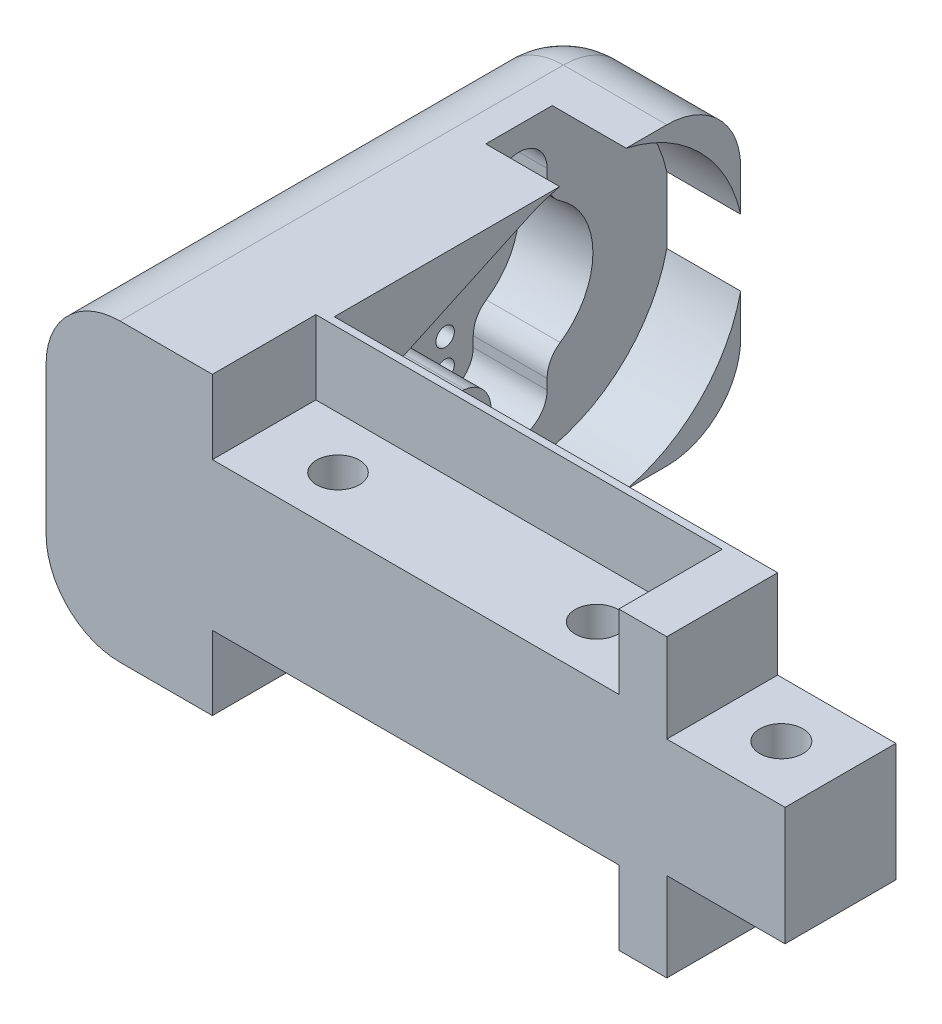
SolidWorks part; units mm, degrees
ref_plane "Спереди" through (0, 0, 0) normal (0, 0, 1) x (1, 0, 0)
ref_plane "Сверху" through (0, 0, 0) normal (0, 1, 0) x (1, 0, 0)
ref_plane "Справа" through (0, 0, 0) normal (1, 0, 0) x (0, 0, -1)
sketch "Эскиз1" plane through (0, 0, 0) normal (0, 1, 0) x (1, 0, 0)
  line L0 (-13, 27.5) -> (-13, 0)
  line L1 (-25, -7.5) -> (25, -7.5)
  line L2 (-25, -7.5) -> (-25, 27.5)
  line L3 (-25, 27.5) -> (-13, 27.5)
  line L4 (25, -7.5) -> (25, 27.5)
  line L5 (-25, -7.5) -> (25, 27.5) construction
  line L6 (-25, 27.5) -> (25, -7.5) construction
  line L7 (-13, 0) -> (13, 0)
  line L8 (13, 0) -> (13, 27.5)
  line L9 (13, 27.5) -> (25, 27.5)
  dimension "D1" = 27.5
  dimension "D2" = 50
  dimension "D3" = 26
  dimension "D4" = 35
extrude "Бобышка-Вытянуть1" add sketch "Эскиз1" along normal blind 20
fillet "Скругление1" radius 5 10 edges at (25, 0, -10) (25, 20, -10) (-25, 20, -10) (-25, 0, -10) (19, 20, -27.5) (25, 10, -27.5) (19, 0, -27.5) (-25, 10, -27.5) (-19, 20, -27.5) (-19, 0, -27.5)
sketch "Эскиз2" plane through (13, 0, 0) normal (-1, 0, 0) x (0, 0, 1)
  line L0 (-1030, 10) -> (48970, 10) construction
  line L1 (-27.5, 5) -> (-27.5, 15) construction
  circle A0 centre (-17.5, 10) radius 8
  point P5 (-27.5, 10)
  dimension "D1" = 16
  dimension "D2" = 10
extrude "Вырез-Вытянуть1" cut sketch "Эскиз2" against normal blind 5
sketch "Эскиз3" plane through (18, 0, 0) normal (-1, 0, 0) x (0, 0, 1)
  circle A0 centre (-17.5, 10) radius 6
  circle A1 centre (-17.5, 10) radius 8 construction
  dimension "D1" = 12
extrude "Вырез-Вытянуть2" cut sketch "Эскиз3" against normal blind 1
sketch "Эскиз4" plane through (-13, 0, 0) normal (1, 0, 0) x (0, 0, -1)
  line L0 (-1015, 10) -> (48985, 10) construction
  line L1 (-7.5, 15) -> (-7.5, 5) construction
  line L2 (13.195, 19.3021) -> (2.9, 14.5376)
  line L3 (2.9, 5.4624) -> (13.195, 0.6979)
  arc A0 (13.195, 0.6979) -> (13.195, 19.3021) centre (17.5, 10) ccw
  circle A1 centre (17.5, 10) radius 8 construction
  arc A2 (2.9, 14.5376) -> (2.9, 5.4624) centre (5, 10) ccw
  point P7 (-7.5, 10)
  dimension "D1" = 20.5
  dimension "D2" = 12.5
  dimension "D3" = 5
extrude "Вырез-Вытянуть3" cut sketch "Эскиз4" against normal blind 5
sketch "Эскиз5" plane through (-18, 0, 0) normal (1, 0, 0) x (0, 0, -1)
  line L0 (19.4, 15.8129) -> (19.4, 16.4984)
  line L1 (15.6, 16.4984) -> (15.6, 15.6654)
  line L2 (13.8328, 13.679) -> (1.9323, 12.2844)
  line L3 (1.9323, 7.7156) -> (13.8328, 6.321)
  line L4 (15.6, 4.3346) -> (15.6, 3.5016)
  line L5 (19.4, 3.5016) -> (19.4, 4.1871)
  arc A0 (19.4, 16.4984) -> (15.6, 16.4984) centre (17.5, 16.4984) ccw
  arc A1 (1.9323, 12.2844) -> (1.9323, 7.7156) centre (2.2, 10) ccw
  arc A2 (15.6, 3.5016) -> (19.4, 3.5016) centre (17.5, 3.5016) ccw
  arc A4 (20.2857, 14.1521) -> (20.2857, 5.8479) centre (17.5, 10) cw
  arc A5 (15.6, 4.3346) -> (13.8328, 6.321) centre (13.6, 4.3346) ccw
  arc A6 (15.6, 15.6654) -> (13.8328, 13.679) centre (13.6, 15.6654) cw
  arc A7 (20.2857, 5.8479) -> (19.4, 4.1871) centre (21.4, 4.1871) ccw
  arc A8 (20.2857, 14.1521) -> (19.4, 15.8129) centre (21.4, 15.8129) cw
  arc A9 (15.25, 20) -> (13.195, 19.3021) centre (17.5, 10) ccw construction
  arc A10 (15.25, 20) -> (13.195, 19.3021) centre (17.5, 10) ccw construction
  dimension "D3" = 2.3
  dimension "D4" = 1.9
  dimension "D5" = 5
  dimension "D8" = 2
  dimension "D9" = 2
  dimension "D1" = 3.8
  dimension "D2" = 15.3
  dimension "D6" = 12.9968
  dimension "D7" = 0.833
extrude "Вырез-Вытянуть4" cut sketch "Эскиз5" against normal blind 5
sketch "Эскиз6" plane through (-23, 0, 0) normal (1, 0, 0) x (0, 0, -1)
  line L0 (-990.222, 10) -> (49009.778, 10) construction
  line L1 (22.5, 5) -> (22.5, 15) construction
  line L2 (17.5, -985.0921) -> (17.5, 49014.9079) construction
  circle A0 centre (2.278, 10) radius 0.625
  circle A1 centre (6.3111, 10) radius 0.625
  circle A2 centre (10.4282, 10) radius 0.625
  circle A3 centre (17.5, 14.9079) radius 0.625
  circle A4 centre (17.5, 16.8489) radius 0.625
  circle A5 centre (17.5, 5.0821) radius 0.625
  circle A6 centre (17.5, 3.1411) radius 0.625
  point P11 (24009.778, 10)
  point P14 (22.5, 10)
  dimension "D1" = 1.25
  dimension "D2" = 4.0331
  dimension "D3" = 4.1171
  dimension "D4" = 12.0718
  dimension "D5" = 4.9079
  dimension "D6" = 1.9409
  dimension "D7" = 4.9179
  dimension "D8" = 1.9409
  dimension "D9" = 5
extrude "Вырез-Вытянуть5" cut sketch "Эскиз6" against normal blind 4
sketch "Эскиз7" plane through (0, 0, 7.5) normal (0, 0, 1) x (1, 0, 0)
  line L0 (-20, 20) -> (20, 20) construction
  line L1 (-13.75, 20) -> (13.75, 20)
  line L2 (-13.75, 20) -> (-13.75, 15)
  line L3 (-13.75, 15) -> (13.75, 15)
  line L4 (13.75, 20) -> (13.75, 15)
  line L5 (-25, 15) -> (-25, 5) construction
  line L6 (25, 15) -> (25, 5) construction
  line L7 (-20, 0) -> (20, 0) construction
  line L8 (-13.75, 0) -> (13.75, 0)
  line L9 (-13.75, 0) -> (-13.75, 5)
  line L10 (-13.75, 5) -> (13.75, 5)
  line L11 (13.75, 0) -> (13.75, 5)
  dimension "D1" = 11.25
  dimension "D2" = 11.25
  dimension "D3" = 5
extrude "Вырез-Вытянуть6" cut sketch "Эскиз7" against normal blind 7
sketch "Эскиз8" plane through (0, 15, 0) normal (0, 1, 0) x (1, 0, 0)
  line L0 (-1013.5, -4) -> (48986.5, -4) construction
  line L1 (-13.75, -0.5) -> (-13.75, -7.5) construction
  line L2 (-13.75, -0.5) -> (-13.75, -7.5) construction
  line L3 (13.75, -0.5) -> (13.75, -7.5) construction
  circle A0 centre (-8.75, -4) radius 1.45
  circle A1 centre (8.75, -4) radius 1.45
  point P9 (-13.75, -4)
  dimension "D1" = 5
  dimension "D2" = 2.9
  dimension "D3" = 5
extrude "Вырез-Вытянуть7" cut sketch "Эскиз8" against normal blind 12
sketch "Эскиз11" plane through (0, 20, 0) normal (0, 1, 0) x (1, 0, 0)
  line L0 (13, 27.5) -> (13, 0)
  line L1 (13, 0) -> (17, 0)
  line L3 (17, 0) -> (17, -7.5)
  line L4 (17, -7.5) -> (25, -7.5)
  line L5 (25, 22.5) -> (25, -7.5) construction
  line L6 (20, -7.5) -> (25, -7.5) construction
  line L7 (25, -7.5) -> (25, 27.5)
  line L8 (25, 27.5) -> (13, 27.5)
  dimension "D1" = 4
extrude "Вырез-Вытянуть8" cut sketch "Эскиз11" against normal blind 6
extrude "Вырез-Вытянуть9" cut sketch "Эскиз11<2>" along normal blind 6 from surface starting at face at (-3.875, 0, -8.0625)
sketch "Эскиз11<2>" plane through (0, 20, 0) normal (0, 1, 0) x (1, 0, 0) same geometry as "Эскиз11"
sketch "Эскиз13" plane through (0, 14, 0) normal (0, 1, 0) x (1, 0, 0)
  line L0 (13, 0) -> (17, 0) construction
  line L1 (13, 27.5) -> (25, 27.5)
  line L2 (13, 27.5) -> (13, 0)
  line L3 (13, 0) -> (25, 0)
  line L4 (25, 27.5) -> (25, 0)
  line L5 (25, -7.5) -> (25, 22.5) construction
extrude "Вырез-Вытянуть10" cut sketch "Эскиз13" against normal blind 11
sketch "Эскиз14" plane through (0, 14, 0) normal (0, 1, 0) x (1, 0, 0)
  line L0 (-975, -3.75) -> (49025, -3.75) construction
  line L1 (25, -7.5) -> (25, 0) construction
  line L2 (21, -1000) -> (21, 49000) construction
  line L4 (17, 0) -> (25, 0) construction
  circle A0 centre (21, -3.75) radius 1.46
  point P7 (25, -3.75)
  point P8 (21, -3.75)
  point P12 (21, 0)
  dimension "D1" = 2.92
extrude "Вырез-Вытянуть11" cut sketch "Эскиз14" against normal blind 11
